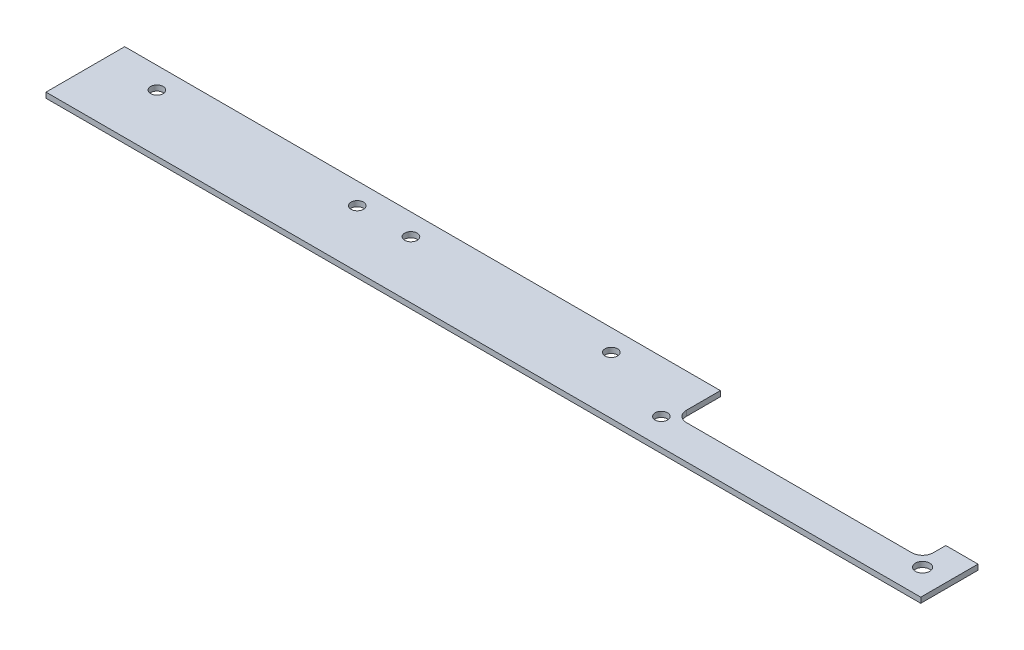
SolidWorks part; units mm, degrees
material "Простая углеродистая сталь"
ref_plane "Спереди" through (0, 0, 0) normal (0, 0, 1) x (1, 0, 0)
ref_plane "Сверху" through (0, 0, 0) normal (0, 1, 0) x (1, 0, 0)
ref_plane "Справа" through (0, 0, 0) normal (1, 0, 0) x (0, 0, -1)
sketch "Эскиз1" plane through (0, 0, 0) normal (0, 1, 0) x (1, 0, 0)
  line L0 (166.5, 22) -> (166.5, 12.5)
  line L1 (0, 0) -> (244.5, 0)
  line L2 (0, 0) -> (0, 22)
  line L3 (0, 22) -> (166.5, 22)
  line L5 (169.5, 9.5) -> (232.5, 9.5)
  line L7 (235.5, 12.5) -> (235.5, 16)
  line L8 (235.5, 16) -> (244.5, 16)
  line L9 (244.5, 16) -> (244.5, 0)
  circle A1 centre (164.5, 7.5) radius 1.75
  circle A2 centre (71, 16) radius 1.75
  circle A3 centre (15, 16) radius 1.75
  circle A4 centre (86, 16) radius 1.75
  circle A5 centre (142, 16) radius 1.75
  circle A8 centre (237.5, 7.5) radius 2
  arc A9 (166.5, 12.5) -> (169.5, 9.5) centre (169.5, 12.5) ccw
  arc A10 (232.5, 9.5) -> (235.5, 12.5) centre (232.5, 12.5) ccw
  dimension "D2" = 3
  dimension "D3" = 3
  dimension "D1" = 2
extrude "Бобышка-Вытянуть1" add sketch "Эскиз1" along normal blind 1.5
